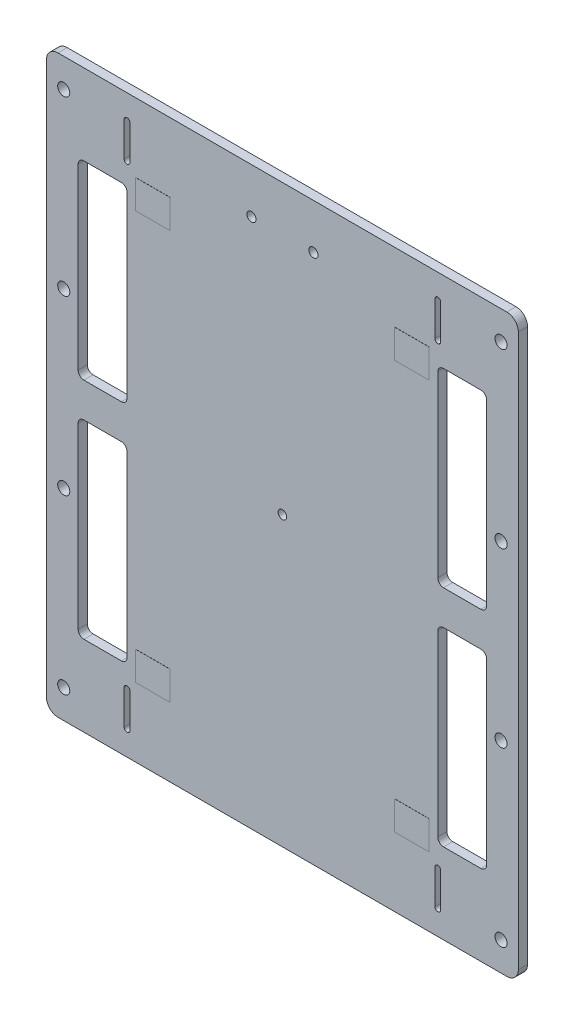
SolidWorks part; units mm, degrees
material "Oshpark board"
ref_plane "Front Plane" through (0, 0, 0) normal (0, 0, 1) x (1, 0, 0)
ref_plane "Top Plane" through (0, 0, 0) normal (0, 1, 0) x (1, 0, 0)
ref_plane "Right Plane" through (0, 0, 0) normal (1, 0, 0) x (0, 0, -1)
sketch "Sketch1" plane through (0, 0, 0) normal (0, 0, 1) x (1, 0, 0)
  line L1 (-39, -50) -> (39, -50)
  line L2 (-41, -48) -> (-41, 48)
  line L3 (-39, 50) -> (39, 50)
  line L4 (41, -48) -> (41, 48)
  line L5 (-41, -50) -> (41, 50) construction
  line L6 (-41, 50) -> (41, -50) construction
  arc A0 (-39, -50) -> (-41, -48) centre (-39, -48) cw
  arc A1 (39, -50) -> (41, -48) centre (39, -48) ccw
  arc A2 (39, 50) -> (41, 48) centre (39, 48) cw
  arc A3 (-41, 48) -> (-39, 50) centre (-39, 48) cw
  point P0 (0, 0)
  dimension "D3" = 2
  dimension "D1" = 100
  dimension "D2" = 82
extrude "boardOutline" add sketch "Sketch1" along normal blind 1.6
sketch "Sketch2" plane through (0, 0, 1.6) normal (0, 0, 1) x (1, 0, 0)
  line L0 (39, 50) -> (-39, 50) construction
  line L1 (-41, 48) -> (-41, -48) construction
  line L3 (-37.5, 44.2) -> (-37.5, 4.2) construction
  circle A0 centre (0, 0) radius 0.75
  circle A1 centre (-37.5, 44.2) radius 1.05 construction
  circle A2 centre (37.5, 44.2) radius 1.05 construction
  circle A3 centre (37.5, 4.2) radius 1.05 construction
  circle A4 centre (37.5, -35.8) radius 1.05 construction
  circle A5 centre (-37.5, 4.2) radius 1.05 construction
  circle A6 centre (-37.5, -35.8) radius 1.05 construction
  circle A7 centre (-5.38, 42.15) radius 0.8
  circle A8 centre (5.39, 42.15) radius 0.8
  dimension "D1" = 1.5
  dimension "D2" = 2.1
  dimension "D9" = 10.77
  dimension "D7" = 1.6
  dimension "D11" = 7.85
  dimension "D12" = 35.62
  dimension "D3" = 5.8
  dimension "D4" = 3.5
  dimension "D8" = 40
  dimension "D10" = 37.5
  dimension "D5" = 2
  dimension "D6" = 3
extrude "componentHoles" cut sketch "Sketch2" against normal through all
sketch "Sketch4" plane through (0, 0, 1.6) normal (0, 0, 1) x (1, 0, 0)
  line L0 (-27, 39.75) -> (-27, 45.75) construction
  line L1 (-27.5, 39.75) -> (-27.5, 45.75)
  line L2 (-26.5, 39.75) -> (-26.5, 45.75)
  line L3 (39, 50) -> (-39, 50) construction
  line L4 (-41, 48) -> (-41, -48) construction
  line L5 (27, 39.75) -> (27, 45.75) construction
  line L6 (26.5, 39.75) -> (26.5, 45.75)
  line L7 (27.5, 39.75) -> (27.5, 45.75)
  line L8 (27, -45.75) -> (27, -39.75) construction
  line L9 (26.5, -45.75) -> (26.5, -39.75)
  line L10 (27.5, -45.75) -> (27.5, -39.75)
  line L11 (-27, -45.75) -> (-27, -39.75) construction
  line L12 (-27.5, -45.75) -> (-27.5, -39.75)
  line L13 (-26.5, -45.75) -> (-26.5, -39.75)
  line L14 (-27, 39.75) -> (27, 39.75) construction
  line L15 (-39, -50) -> (39, -50) construction
  arc A0 (-27.5, 39.75) -> (-26.5, 39.75) centre (-27, 39.75) ccw
  arc A1 (-26.5, 45.75) -> (-27.5, 45.75) centre (-27, 45.75) ccw
  arc A2 (26.5, 39.75) -> (27.5, 39.75) centre (27, 39.75) ccw
  arc A3 (27.5, 45.75) -> (26.5, 45.75) centre (27, 45.75) ccw
  arc A4 (26.5, -45.75) -> (27.5, -45.75) centre (27, -45.75) ccw
  arc A5 (27.5, -39.75) -> (26.5, -39.75) centre (27, -39.75) ccw
  arc A6 (-27.5, -45.75) -> (-26.5, -45.75) centre (-27, -45.75) ccw
  arc A7 (-26.5, -39.75) -> (-27.5, -39.75) centre (-27, -39.75) ccw
  point P2 (-27, 42.75)
  point P16 (27, 42.75)
  point P23 (27, -42.75)
  point P30 (-27, -42.75)
  dimension "D1" = 4.25
  dimension "D2" = 13.5
  dimension "D3" = 1
  dimension "D4" = 6
  dimension "D7" = 54
  dimension "D8" = 14
  dimension "D9" = 4.25
  dimension "D10" = 4.25
  dimension "D5" = 2
  dimension "D6" = 2
extrude "solarCellContactHoles" cut sketch "Sketch4" against normal blind 1.6
sketch "Sketch3" plane through (0, 0, 1.6) normal (0, 0, 1) x (1, 0, 0)
  line L1 (-34.5, 36) -> (-28, 36)
  line L2 (-35.5, 35) -> (-35.5, 4)
  line L3 (-34.5, 3) -> (-28, 3)
  line L4 (-27, 35) -> (-27, 4)
  line L5 (-41, 48) -> (-41, -48) construction
  line L6 (41, 0) -> (-41, 0) construction
  line L7 (41, -48) -> (41, 48) construction
  line L8 (-41, 48) -> (-41, -48) construction
  line L9 (0, 50) -> (0, -50) construction
  line L10 (39, 50) -> (-39, 50) construction
  line L11 (-39, -50) -> (39, -50) construction
  line L12 (-34.5, -36) -> (-28, -36)
  line L13 (-35.5, -35) -> (-35.5, -4)
  line L14 (-34.5, -3) -> (-28, -3)
  line L15 (-27, -35) -> (-27, -4)
  line L16 (34.5, -36) -> (28, -36)
  line L17 (27, -35) -> (27, -4)
  line L18 (34.5, -3) -> (28, -3)
  line L20 (35.5, -35) -> (35.5, -4)
  line L21 (34.5, 36) -> (28, 36)
  line L22 (35.5, 35) -> (35.5, 4)
  line L23 (34.5, 3) -> (28, 3)
  line L24 (27, 35) -> (27, 4)
  arc A0 (-35.5, 4) -> (-34.5, 3) centre (-34.5, 4) ccw
  arc A1 (-28, 3) -> (-27, 4) centre (-28, 4) ccw
  arc A2 (-28, 36) -> (-27, 35) centre (-28, 35) cw
  arc A3 (-34.5, 36) -> (-35.5, 35) centre (-34.5, 35) ccw
  arc A5 (-28, -36) -> (-27, -35) centre (-28, -35) ccw
  arc A6 (-34.5, -36) -> (-35.5, -35) centre (-34.5, -35) cw
  arc A7 (-35.5, -4) -> (-34.5, -3) centre (-34.5, -4) cw
  arc A8 (-28, -3) -> (-27, -4) centre (-28, -4) cw
  arc A9 (34.5, -36) -> (35.5, -35) centre (34.5, -35) ccw
  arc A10 (28, -36) -> (27, -35) centre (28, -35) cw
  arc A11 (28, -3) -> (27, -4) centre (28, -4) ccw
  arc A12 (35.5, -4) -> (34.5, -3) centre (34.5, -4) ccw
  arc A13 (28, 36) -> (27, 35) centre (28, 35) ccw
  arc A14 (34.5, 36) -> (35.5, 35) centre (34.5, 35) cw
  arc A15 (35.5, 4) -> (34.5, 3) centre (34.5, 4) cw
  arc A16 (28, 3) -> (27, 4) centre (28, 4) cw
  point P12 (-27, 3)
  point P15 (-27, 36)
  point P18 (-35.5, 36)
  dimension "D5" = 1
  dimension "D1" = 8.5
  dimension "D2" = 33
  dimension "D3" = 14
  dimension "D4" = 5.5
extrude "windows" cut sketch "Sketch3" against normal through all
sketch "Sketch5" plane through (0, 0, 1.6) normal (0, 0, 1) x (1, 0, 0)
  line L0 (-41, 48) -> (-41, -48) construction
  line L1 (-25.5, 38) -> (-19.5, 38)
  line L2 (-25.5, 38) -> (-25.5, 33)
  line L3 (-25.5, 33) -> (-19.5, 33)
  line L4 (-19.5, 38) -> (-19.5, 33)
  line L5 (39, 50) -> (-39, 50) construction
  line L6 (19.5, 38) -> (19.5, 33)
  line L7 (25.5, 38) -> (25.5, 33)
  line L8 (19.5, 33) -> (25.5, 33)
  line L9 (19.5, 38) -> (25.5, 38)
  line L10 (19.5, -33) -> (19.5, -38)
  line L11 (25.5, -33) -> (25.5, -38)
  line L12 (19.5, -38) -> (25.5, -38)
  line L13 (19.5, -33) -> (25.5, -33)
  line L14 (-25.5, -33) -> (-25.5, -38)
  line L15 (-19.5, -33) -> (-19.5, -38)
  line L16 (-25.5, -38) -> (-19.5, -38)
  line L17 (-25.5, -33) -> (-19.5, -33)
  line L18 (-25.5, 38) -> (19.5, 38) construction
  line L19 (-25.5, 38) -> (-25.5, -33) construction
  dimension "D1" = 5
  dimension "D2" = 6
  dimension "D3" = 15.5
  dimension "D4" = 12
  dimension "D7" = 45
  dimension "D8" = 71
  dimension "D5" = 2
  dimension "D6" = 2
extrude "contactPads" add sketch "Sketch5" along normal blind 0.02
hole_wizard "M2 Clearance Hole1" positions "Sketch6" profile "Sketch7" hole size "M2" standard "ANSI Metric" end condition through all
sketch "Sketch6" plane through (0, 0, 0) normal (0, 0, -1) x (-1, 0, 0)
  line L4 (0, -40.934) -> (0, 34.4116) construction
  line L5 (-38, -50) -> (-38, -45) construction
  line L6 (39, -50) -> (-39, -50) construction
  line L7 (-38, -45) -> (-38, -15) construction
  line L8 (-38, -15) -> (-38, 15) construction
  line L9 (-38, 15) -> (-38, 45) construction
  line L10 (-38, 45) -> (-38, 50) construction
  line L11 (-39, 50) -> (39, 50) construction
  line L13 (-41, -48) -> (-41, 48) construction
  point P0 (-38, 45)
  point P27 (-38, -15)
  point P36 (-38, -45)
  point P38 (-38, 15)
  point P59 (38, -45)
  point P60 (38, -15)
  point P61 (38, 15)
  point P62 (38, 45)
  dimension "D1" = 3
  dimension "D2" = 5
sketch "Sketch7" plane through (38, 45, 0) normal (1, 0, 0) x (0, 1, 0)
  line L0 (0, 0) -> (0, 1.62)
  line L1 (0, 1.62) -> (1.05, 1.62)
  line L2 (1.05, 1.62) -> (1.05, 0)
  line L5 (1.05, 0) -> (0, 0)
  line L11 (0, -6.35) -> (0, 107.95) construction
  dimension "Thru Hole Dia." = 2.1
  dimension "Thru Hole Depth" = 1.62
sketch "Sketch8" plane through (0, 0, 1.6) normal (0, 0, 1) x (1, 0, 0)
  line L0 (-15, -11.3) -> (-15, 19.7)
  line L1 (-15, -11.3) -> (-15, 19.7)
  line L2 (12, -14.3) -> (-12, -14.3)
  line L3 (12, -14.3) -> (-12, -14.3)
  line L4 (15, 19.7) -> (15, -11.3)
  line L5 (15, 19.7) -> (15, -11.3)
  line L6 (-12, 22.7) -> (12, 22.7)
  line L7 (-12, 22.7) -> (12, 22.7)
  line L8 (-32.5, 22.7) -> (-21, 22.7)
  line L9 (-32.5, 22.7) -> (-21, 22.7)
  line L10 (-35.5, 19.7) -> (-35.5, -11.3)
  line L11 (-35.5, 19.7) -> (-35.5, -11.3)
  line L12 (-21, -14.3) -> (-32.5, -14.3)
  line L13 (-21, -14.3) -> (-32.5, -14.3)
  line L14 (-18, 19.7) -> (-18, -11.3)
  line L15 (-18, 19.7) -> (-18, -11.3)
  line L16 (18, -11.3) -> (18, 19.7)
  line L17 (18, -11.3) -> (18, 19.7)
  line L18 (32.5, -14.3) -> (21, -14.3)
  line L19 (32.5, -14.3) -> (21, -14.3)
  line L20 (35.5, -11.3) -> (35.5, 19.7)
  line L21 (35.5, -11.3) -> (35.5, 19.7)
  line L22 (21, 22.7) -> (32.5, 22.7)
  line L23 (21, 22.7) -> (32.5, 22.7)
  line L24 (-15, -43) -> (-15, -20.3)
  line L25 (-15, -43) -> (-15, -20.3)
  line L26 (12, -46) -> (-12, -46)
  line L27 (12, -46) -> (-12, -46)
  line L28 (15, -20.3) -> (15, -43)
  line L29 (15, -20.3) -> (15, -43)
  line L30 (-12, -17.3) -> (12, -17.3)
  line L31 (-12, -17.3) -> (12, -17.3)
  line L32 (-35.5, -20.3) -> (-35.5, -43)
  line L33 (-35.5, -20.3) -> (-35.5, -43)
  line L34 (-32.5, -17.3) -> (-21, -17.3)
  line L35 (-32.5, -17.3) -> (-21, -17.3)
  line L36 (-18, -20.3) -> (-18, -43)
  line L37 (-18, -20.3) -> (-18, -43)
  line L38 (-21, -46) -> (-32.5, -46)
  line L39 (-21, -46) -> (-32.5, -46)
  line L40 (18, -43) -> (18, -20.3)
  line L41 (18, -43) -> (18, -20.3)
  line L42 (32.5, -46) -> (21, -46)
  line L43 (32.5, -46) -> (21, -46)
  line L44 (35.5, -43) -> (35.5, -20.3)
  line L45 (35.5, -43) -> (35.5, -20.3)
  line L46 (21, -17.3) -> (32.5, -17.3)
  line L47 (21, -17.3) -> (32.5, -17.3)
  line L48 (-15, 28.7) -> (-15, 42)
  line L49 (-15, 28.7) -> (-15, 42)
  line L50 (12, 25.7) -> (-12, 25.7)
  line L51 (12, 25.7) -> (-12, 25.7)
  line L52 (15, 42) -> (15, 28.7)
  line L53 (15, 42) -> (15, 28.7)
  line L54 (12, 45) -> (-12, 45)
  line L55 (12, 45) -> (-12, 45)
  line L56 (-35.5, 42) -> (-35.5, 28.7)
  line L57 (-35.5, 42) -> (-35.5, 28.7)
  line L58 (-21, 25.7) -> (-32.5, 25.7)
  line L59 (-21, 25.7) -> (-32.5, 25.7)
  line L60 (-18, 42) -> (-18, 28.7)
  line L61 (-18, 42) -> (-18, 28.7)
  line L62 (-21, 45) -> (-32.5, 45)
  line L63 (-21, 45) -> (-32.5, 45)
  line L64 (18, 28.7) -> (18, 42)
  line L65 (18, 28.7) -> (18, 42)
  line L66 (32.5, 25.7) -> (21, 25.7)
  line L67 (32.5, 25.7) -> (21, 25.7)
  line L68 (35.5, 28.7) -> (35.5, 42)
  line L69 (35.5, 28.7) -> (35.5, 42)
  line L70 (32.5, 45) -> (21, 45)
  line L71 (32.5, 45) -> (21, 45)
  line L72 (-32.5, -49) -> (-21, -49)
  line L73 (-32.5, -49) -> (-21, -49)
  line L74 (-12, -49) -> (12, -49)
  line L75 (-12, -49) -> (12, -49)
  line L76 (21, -49) -> (32.5, -49)
  line L77 (21, -49) -> (32.5, -49)
  line L78 (-39, -50) -> (39, -50) construction
  line L79 (41, -48) -> (41, 48) construction
  line L80 (39, 50) -> (-39, 50) construction
  line L81 (-41, 48) -> (-41, -48) construction
  line L82 (-39, -50) -> (39, -50)
  line L83 (41, -48) -> (41, 48)
  line L84 (39, 50) -> (-39, 50)
  line L85 (-41, 48) -> (-41, -48)
  arc A0 (-15, -11.3) -> (-12, -14.3) centre (-12, -11.3) ccw
  arc A1 (-15, -11.3) -> (-12, -14.3) centre (-12, -11.3) ccw
  arc A2 (12, -14.3) -> (15, -11.3) centre (12, -11.3) ccw
  arc A3 (12, -14.3) -> (15, -11.3) centre (12, -11.3) ccw
  arc A4 (15, 19.7) -> (12, 22.7) centre (12, 19.7) ccw
  arc A5 (15, 19.7) -> (12, 22.7) centre (12, 19.7) ccw
  arc A6 (-12, 22.7) -> (-15, 19.7) centre (-12, 19.7) ccw
  arc A7 (-12, 22.7) -> (-15, 19.7) centre (-12, 19.7) ccw
  arc A8 (-18, 19.7) -> (-21, 22.7) centre (-21, 19.7) ccw
  arc A9 (-18, 19.7) -> (-21, 22.7) centre (-21, 19.7) ccw
  arc A10 (-32.5, 22.7) -> (-35.5, 19.7) centre (-32.5, 19.7) ccw
  arc A11 (-32.5, 22.7) -> (-35.5, 19.7) centre (-32.5, 19.7) ccw
  arc A12 (-35.5, -11.3) -> (-32.5, -14.3) centre (-32.5, -11.3) ccw
  arc A13 (-35.5, -11.3) -> (-32.5, -14.3) centre (-32.5, -11.3) ccw
  arc A14 (-21, -14.3) -> (-18, -11.3) centre (-21, -11.3) ccw
  arc A15 (-21, -14.3) -> (-18, -11.3) centre (-21, -11.3) ccw
  arc A16 (18, -11.3) -> (21, -14.3) centre (21, -11.3) ccw
  arc A17 (18, -11.3) -> (21, -14.3) centre (21, -11.3) ccw
  arc A18 (32.5, -14.3) -> (35.5, -11.3) centre (32.5, -11.3) ccw
  arc A19 (32.5, -14.3) -> (35.5, -11.3) centre (32.5, -11.3) ccw
  arc A20 (35.5, 19.7) -> (32.5, 22.7) centre (32.5, 19.7) ccw
  arc A21 (35.5, 19.7) -> (32.5, 22.7) centre (32.5, 19.7) ccw
  arc A22 (21, 22.7) -> (18, 19.7) centre (21, 19.7) ccw
  arc A23 (21, 22.7) -> (18, 19.7) centre (21, 19.7) ccw
  arc A24 (-15, -43) -> (-12, -46) centre (-12, -43) ccw
  arc A25 (-15, -43) -> (-12, -46) centre (-12, -43) ccw
  arc A26 (12, -46) -> (15, -43) centre (12, -43) ccw
  arc A27 (12, -46) -> (15, -43) centre (12, -43) ccw
  arc A28 (15, -20.3) -> (12, -17.3) centre (12, -20.3) ccw
  arc A29 (15, -20.3) -> (12, -17.3) centre (12, -20.3) ccw
  arc A30 (-12, -17.3) -> (-15, -20.3) centre (-12, -20.3) ccw
  arc A31 (-12, -17.3) -> (-15, -20.3) centre (-12, -20.3) ccw
  arc A32 (-32.5, -17.3) -> (-35.5, -20.3) centre (-32.5, -20.3) ccw
  arc A33 (-32.5, -17.3) -> (-35.5, -20.3) centre (-32.5, -20.3) ccw
  arc A34 (-18, -20.3) -> (-21, -17.3) centre (-21, -20.3) ccw
  arc A35 (-18, -20.3) -> (-21, -17.3) centre (-21, -20.3) ccw
  arc A36 (-21, -46) -> (-18, -43) centre (-21, -43) ccw
  arc A37 (-21, -46) -> (-18, -43) centre (-21, -43) ccw
  arc A38 (-35.5, -43) -> (-32.5, -46) centre (-32.5, -43) ccw
  arc A39 (-35.5, -43) -> (-32.5, -46) centre (-32.5, -43) ccw
  arc A40 (18, -43) -> (21, -46) centre (21, -43) ccw
  arc A41 (18, -43) -> (21, -46) centre (21, -43) ccw
  arc A42 (32.5, -46) -> (35.5, -43) centre (32.5, -43) ccw
  arc A43 (32.5, -46) -> (35.5, -43) centre (32.5, -43) ccw
  arc A44 (35.5, -20.3) -> (32.5, -17.3) centre (32.5, -20.3) ccw
  arc A45 (35.5, -20.3) -> (32.5, -17.3) centre (32.5, -20.3) ccw
  arc A46 (21, -17.3) -> (18, -20.3) centre (21, -20.3) ccw
  arc A47 (21, -17.3) -> (18, -20.3) centre (21, -20.3) ccw
  arc A48 (-15, 28.7) -> (-12, 25.7) centre (-12, 28.7) ccw
  arc A49 (-15, 28.7) -> (-12, 25.7) centre (-12, 28.7) ccw
  arc A50 (12, 25.7) -> (15, 28.7) centre (12, 28.7) ccw
  arc A51 (12, 25.7) -> (15, 28.7) centre (12, 28.7) ccw
  arc A52 (15, 42) -> (12, 45) centre (12, 42) ccw
  arc A53 (15, 42) -> (12, 45) centre (12, 42) ccw
  arc A54 (-12, 45) -> (-15, 42) centre (-12, 42) ccw
  arc A55 (-12, 45) -> (-15, 42) centre (-12, 42) ccw
  arc A56 (-35.5, 28.7) -> (-32.5, 25.7) centre (-32.5, 28.7) ccw
  arc A57 (-35.5, 28.7) -> (-32.5, 25.7) centre (-32.5, 28.7) ccw
  arc A58 (-21, 25.7) -> (-18, 28.7) centre (-21, 28.7) ccw
  arc A59 (-21, 25.7) -> (-18, 28.7) centre (-21, 28.7) ccw
  arc A60 (-18, 42) -> (-21, 45) centre (-21, 42) ccw
  arc A61 (-18, 42) -> (-21, 45) centre (-21, 42) ccw
  arc A62 (-32.5, 45) -> (-35.5, 42) centre (-32.5, 42) ccw
  arc A63 (-32.5, 45) -> (-35.5, 42) centre (-32.5, 42) ccw
  arc A64 (18, 28.7) -> (21, 25.7) centre (21, 28.7) ccw
  arc A65 (18, 28.7) -> (21, 25.7) centre (21, 28.7) ccw
  arc A66 (32.5, 25.7) -> (35.5, 28.7) centre (32.5, 28.7) ccw
  arc A67 (32.5, 25.7) -> (35.5, 28.7) centre (32.5, 28.7) ccw
  arc A68 (35.5, 42) -> (32.5, 45) centre (32.5, 42) ccw
  arc A69 (35.5, 42) -> (32.5, 45) centre (32.5, 42) ccw
  arc A70 (21, 45) -> (18, 42) centre (21, 42) ccw
  arc A71 (21, 45) -> (18, 42) centre (21, 42) ccw
  arc A72 (-32.5, -49) -> (-35.5, -52) centre (-32.5, -52) ccw
  arc A73 (-32.5, -49) -> (-34.7361, -50) centre (-32.5, -52) ccw
  arc A74 (-18, -52) -> (-21, -49) centre (-21, -52) ccw
  arc A75 (-18.7639, -50) -> (-21, -49) centre (-21, -52) ccw
  arc A76 (-12, -49) -> (-15, -52) centre (-12, -52) ccw
  arc A77 (-12, -49) -> (-14.2361, -50) centre (-12, -52) ccw
  arc A78 (15, -52) -> (12, -49) centre (12, -52) ccw
  arc A79 (14.2361, -50) -> (12, -49) centre (12, -52) ccw
  arc A80 (21, -49) -> (18, -52) centre (21, -52) ccw
  arc A81 (21, -49) -> (18.7639, -50) centre (21, -52) ccw
  arc A82 (35.5, -52) -> (32.5, -49) centre (32.5, -52) ccw
  arc A83 (34.7361, -50) -> (32.5, -49) centre (32.5, -52) ccw
  arc A84 (-41, -48) -> (-39, -50) centre (-39, -48) ccw construction
  arc A85 (39, -50) -> (41, -48) centre (39, -48) ccw construction
  arc A86 (41, 48) -> (39, 50) centre (39, 48) ccw construction
  arc A87 (-39, 50) -> (-41, 48) centre (-39, 48) ccw construction
  arc A88 (-41, -48) -> (-39, -50) centre (-39, -48) ccw
  arc A89 (39, -50) -> (41, -48) centre (39, -48) ccw
  arc A90 (41, 48) -> (39, 50) centre (39, 48) ccw
  arc A91 (-39, 50) -> (-41, 48) centre (-39, 48) ccw
